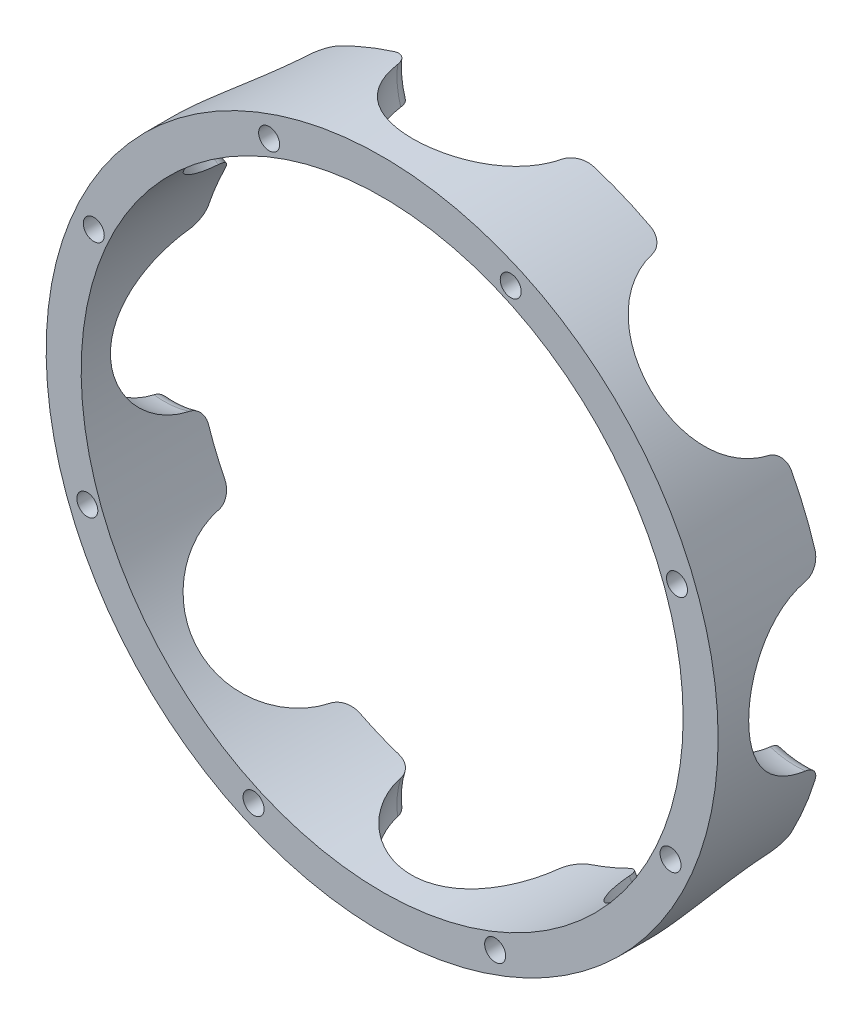
SolidWorks part; units mm, degrees
ref_plane "Front Plane" through (0, 0, 0) normal (0, 0, 1) x (1, 0, 0)
ref_plane "Top Plane" through (0, 0, 0) normal (0, 1, 0) x (1, 0, 0)
ref_plane "Right Plane" through (0, 0, 0) normal (1, 0, 0) x (0, 0, -1)
sketch "Sketch1" plane through (0, 0, 0) normal (0, 0, 1) x (1, 0, 0)
  circle A0 centre (0, 0) radius 48
  circle A1 centre (0, 0) radius 43
  dimension "D1" = 96
  dimension "D2" = 86
extrude "Boss-Extrude2" add sketch "Sketch1" along normal blind 16
sketch "Sketch2" plane through (0, 0, 0) normal (0, 0, 1) x (1, 0, 0)
  line L0 (0, 68.5785) -> (0, -63.0172) construction
  line L1 (0, 57.0725) -> (0, 33.0725)
  circle A0 centre (0, 0) radius 45 construction
  arc A2 (0, 57.0725) -> (0, 33.0725) centre (0, 45.0725) cw
  dimension "D1" = 90
  dimension "D2" = 12
revolve "Cut-Revolve1" cut sketch "Sketch2" angle 360 about L0
fillet "Fillet1" radius 2.5 2 edges at (-11.9473, 43.9486, 0) (11.9473, 43.9486, 0)
pattern_circular "CirPattern1" count 8 over 360 about axis through (0, 0, 16) along (0, 0, -1) of "Cut-Revolve1"
sketch "Sketch4" plane through (0, 0, 0) normal (0, 0, -1) x (-1, 0, 0)
  circle A0 centre (-41.1992, -18.3688) radius 1.5
  dimension "D1" = 3
extrude "Cut-Extrude1" cut sketch "Sketch4" against normal blind 16
pattern_circular "CirPattern2" count 8 over 360 about axis through (0, 0, 16) along (0, 0, -1) of "Cut-Extrude1" reverse direction yes
fillet "Fillet2" radius 2.5 14 edges at (-39.5243, 22.6283, 0) (-22.6283, 39.5243, 0) (-43.9486, -11.9473, 0) (-43.9486, 11.9473, 0) (-22.6283, -39.5243, 0) (-39.5243, -22.6283, 0) (-11.9473, -43.9486, 0) (11.9473, -43.9486, 0) (39.5243, 22.6283, 0) (22.6283, 39.5243, 0) (43.9486, -11.9473, 0) (43.9486, 11.9473, 0) (22.6283, -39.5243, 0) (39.5243, -22.6283, 0)
equation "\"359d\"=360"
